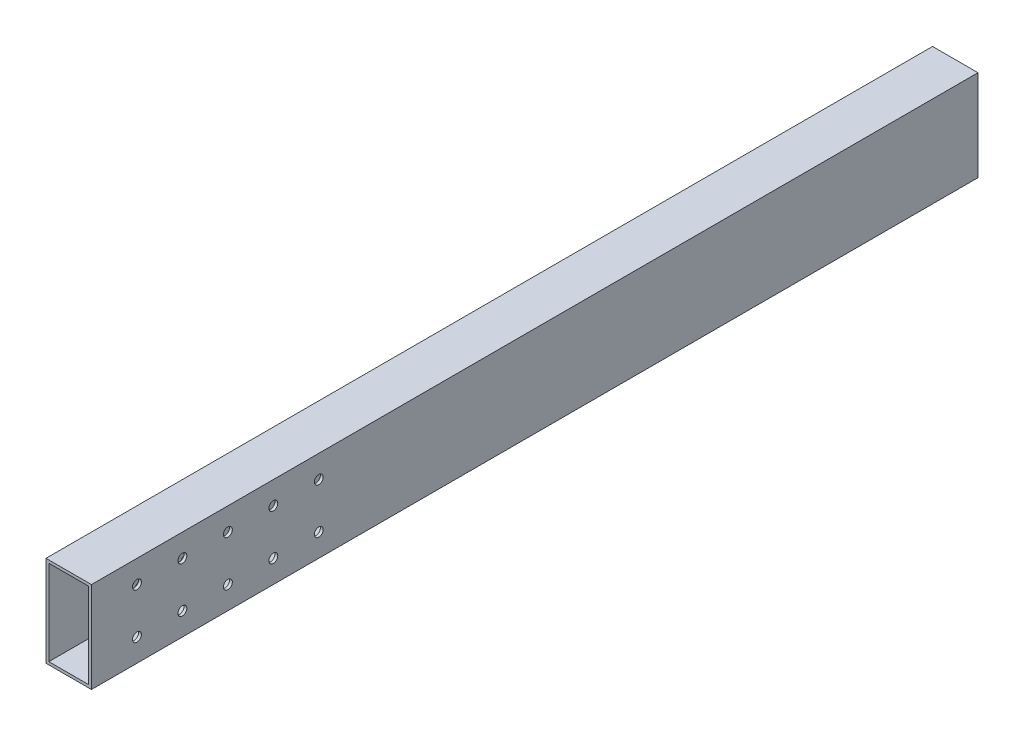
SolidWorks part; units mm, degrees
material "6061-T4 (SS)"
ref_plane "Front Plane" through (0, 0, 0) normal (0, 0, 1) x (1, 0, 0)
ref_plane "Top Plane" through (0, 0, 0) normal (0, 1, 0) x (1, 0, 0)
ref_plane "Right Plane" through (0, 0, 0) normal (1, 0, 0) x (0, 0, -1)
sketch "Sketch1" plane through (0, 0, 0) normal (0, 0, 1) x (1, 0, 0)
  line L0 (1.5875, 49.2125) -> (23.8125, 49.2125)
  line L5 (0, 0) -> (25.4, 0)
  line L6 (0, 0) -> (0, 50.8)
  line L7 (0, 50.8) -> (25.4, 50.8)
  line L8 (25.4, 0) -> (25.4, 50.8)
  line L13 (23.8125, 1.5875) -> (23.8125, 49.2125)
  line L14 (1.5875, 1.5875) -> (23.8125, 1.5875)
  line L15 (1.5875, 1.5875) -> (1.5875, 49.2125)
  dimension "D1" = 25.4
  dimension "D2" = 1.5875
  dimension "D3" = 50.8
extrude "Boss-Extrude1" add sketch "Sketch1" along normal blind 495.3
sketch "Sketch2" plane through (25.4, 0, 0) normal (-1, 0, 0) x (0, 0, 1)
  line L0 (495.3, 50.8) -> (495.3, 0) construction
  line L1 (495.3, 50.8) -> (0, 50.8) construction
  circle A16 centre (444.5, 38.1) radius 2.4892
  circle A17 centre (419.1, 38.1) radius 2.4892
  circle A18 centre (393.7, 38.1) radius 2.4892
  circle A19 centre (368.3, 38.1) radius 2.4892
  circle A21 centre (444.5, 12.7) radius 2.4892
  circle A22 centre (419.1, 12.7) radius 2.4892
  circle A23 centre (393.7, 12.7) radius 2.4892
  circle A24 centre (368.3, 12.7) radius 2.4892
  circle A26 centre (469.9, 12.7) radius 2.4892
  circle A29 centre (469.9, 38.1) radius 2.4892
  circle A30 centre (342.9, 38.1) radius 2.4892 [skipped]
  circle A31 centre (342.9, 12.7) radius 2.4892 [skipped]
  dimension "D4" = 25.4
  dimension "D5" = 6
  dimension "D6" = 2
  dimension "D1" = 4.9784
  dimension "D7" = 12.7
  dimension "D2" = 25.4
  dimension "D3" = 25.4
extrude "Cut-Extrude1" cut sketch "Sketch2" along normal up to next contours A24 | A23 | A18 | A19
sketch "Sketch3" plane through (0, 0, 0) normal (-1, 0, 0) x (0, 0, 1)
  line L0 (495.3, 25.4) -> (0, 25.4) construction
  line L1 (495.3, 50.8) -> (495.3, 0) construction
  line L2 (0, 50.8) -> (0, 0) construction
  line L4 (88.9, 41.275) -> (139.7, 41.275) construction
  line L5 (88.9, 41.275) -> (88.9, 9.525) construction
  line L6 (88.9, 9.525) -> (139.7, 9.525) construction
  line L7 (139.7, 41.275) -> (139.7, 9.525) construction
  line L8 (88.9, 41.275) -> (139.7, 9.525) construction
  line L9 (88.9, 9.525) -> (139.7, 41.275) construction
  circle A0 centre (114.3, 25.4) radius 14.2875
  circle A1 centre (139.7, 41.275) radius 2.4892
  circle A2 centre (88.9, 41.275) radius 2.4892
  circle A3 centre (88.9, 9.525) radius 2.4892
  circle A4 centre (139.7, 9.525) radius 2.4892
  dimension "D1" = 28.575
  dimension "D2" = 114.3
  dimension "D5" = 4.9784
  dimension "D3" = 15.875
  dimension "D4" = 25.4
extrude "Cut-Extrude2" cut sketch "Sketch3" against normal up to next
extrude "Cut-Extrude5" cut sketch "Sketch2<3>" along normal through all contours A22 | A17 | A26 | A29 | A16 | A21 region at (25.4, 38.1, 444.5) region at (25.4, 38.1, 419.1) region at (25.4, 12.7, 444.5) region at (25.4, 12.7, 419.1) region at (25.4, 12.7, 469.9) region at (25.4, 38.1, 469.9)
sketch "Sketch2<3>" plane through (25.4, 0, 0) normal (-1, 0, 0) x (0, 0, 1) same geometry as "Sketch2"
sketch "Sketch4" plane through (0, 0, 0) normal (-1, 0, 0) x (0, 0, 1)
  line L0 (0, 50.8) -> (0, 0) construction
  line L2 (495.3, 0) -> (0, 0) construction
  circle A0 centre (12.7, 38.1) radius 2.4892
  circle A1 centre (25.4, 38.1) radius 2.4892
  circle A2 centre (38.1, 38.1) radius 2.4892
  circle A3 centre (25.4, 12.7) radius 2.4892
  circle A4 centre (38.1, 12.7) radius 2.4892
  circle A5 centre (12.7, 12.7) radius 2.4892
  point P16 (0, 0)
  point P17 (25.4, 12.7)
  point P18 (38.1, 38.1)
  point P19 (23.0337, 12.7)
  dimension "D1" = 4.9784
  dimension "D7" = 12.7
  dimension "D4" = 25.4
  dimension "D5" = 12.7
  dimension "D6" = 12.7
  dimension "D2" = 3
  dimension "D3" = 2
extrude "Cut-Extrude6" cut sketch "Sketch4" against normal up to next
